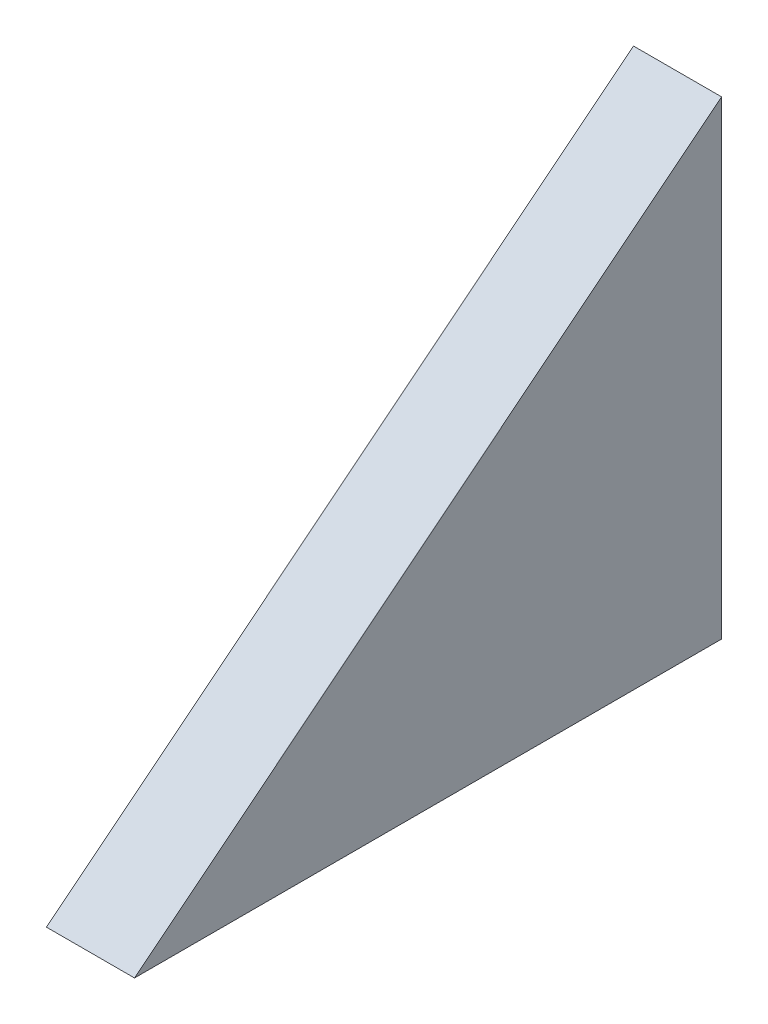
SolidWorks part; units mm, degrees
ref_plane "Front Plane" through (0, 0, 0) normal (0, 0, 1) x (1, 0, 0)
ref_plane "Top Plane" through (0, 0, 0) normal (0, 1, 0) x (1, 0, 0)
ref_plane "Right Plane" through (0, 0, 0) normal (1, 0, 0) x (0, 0, -1)
sketch "Sketch1" plane through (0, 0, 0) normal (1, 0, 0) x (0, 0, -1)
  line L0 (-41.2627, 95.2148) -> (-168.2627, -6.3852)
  line L1 (-168.2627, -6.3852) -> (-41.2627, -6.3852)
  line L2 (-41.2627, 95.2148) -> (-41.2627, -6.3852)
extrude "Boss-Extrude1" add sketch "Sketch1" along normal blind 19.05 contours L2 L1 L0
